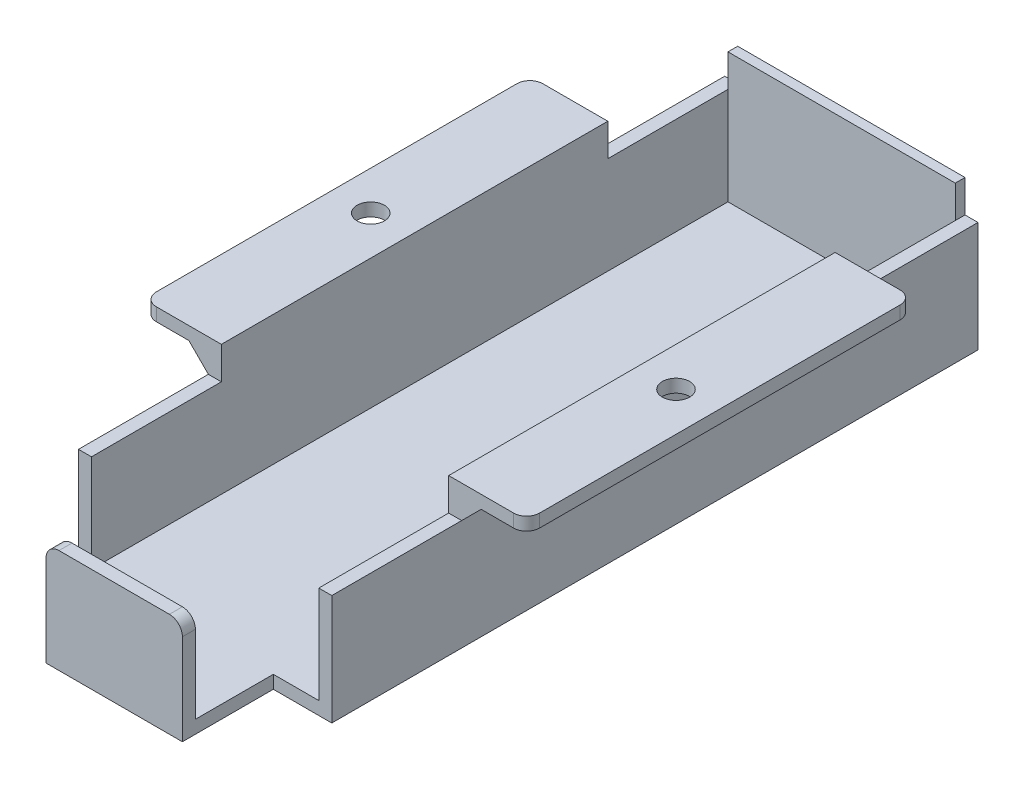
SolidWorks part; units mm, degrees
ref_plane "Front Plane" through (0, 0, 0) normal (0, 0, 1) x (1, 0, 0)
ref_plane "Top Plane" through (0, 0, 0) normal (0, 1, 0) x (1, 0, 0)
ref_plane "Right Plane" through (0, 0, 0) normal (1, 0, 0) x (0, 0, -1)
sketch "Sketch1" plane through (0, 0, 0) normal (0, 0, 1) x (1, 0, 0)
  line L0 (-29.5, 0) -> (-17.5, 0)
  line L1 (-17.5, 0) -> (-17.5, -20)
  line L2 (-17.5, -20) -> (17.5, -20)
  line L3 (0, -618.9467) -> (0, 30328.3864) construction
  line L5 (29.5, -2) -> (29.5, 0)
  line L6 (19.5, -2) -> (29.5, -2)
  line L7 (19.5, -22) -> (19.5, -2)
  line L8 (19.5, -22) -> (-19.5, -22)
  line L9 (-19.5, -22) -> (-19.5, -2)
  line L10 (-19.5, -2) -> (-29.5, -2)
  line L11 (-29.5, -2) -> (-29.5, 0)
  line L12 (17.5, 0) -> (17.5, -20)
  line L13 (29.5, 0) -> (17.5, 0)
  dimension "D1" = 35
  dimension "D2" = 20
  dimension "D3" = 2
  dimension "D4" = 2
  dimension "D5" = 2
  dimension "D6" = 10
extrude "Boss-Extrude1" add sketch "Sketch1" along normal mid plane 98
sketch "Sketch3" plane through (0, 0, 0) normal (1, 0, 0) x (0, 0, -1)
  line L0 (-49, -22) -> (-63, -22)
  line L1 (-63, -22) -> (-63, -6)
  line L2 (-63, -6) -> (-61, -6)
  line L3 (-61, -6) -> (-61, -20)
  line L4 (-61, -20) -> (-49, -20)
  line L5 (-49, -22) -> (-49, -2) construction
  line L6 (-49, -20) -> (-49, -22)
  line L8 (49, -20) -> (49, 0) construction
  dimension "D2" = 2
  dimension "D4" = 16
  dimension "D1" = 110
extrude "Boss-Extrude3" add sketch "Sketch3" along normal mid plane 21
chamfer "Chamfer1" distance 3 angle 45 2 edges at (19.5, -2, 0) (-19.5, -2, 0)
sketch "Sketch4" plane through (0, 0, 0) normal (0, 1, 0) x (1, 0, 0)
  line L0 (-23.5, 0) -> (23.5, 0) construction
  circle A0 centre (-23.5, 0) radius 2.1
  circle A1 centre (23.5, 0) radius 2.1
  point P4 (0, 0)
  dimension "D1" = 4.2
  dimension "D2" = 4.2
  dimension "D3" = 47
extrude "Cut-Extrude1" cut sketch "Sketch4" against normal through all
sketch "Sketch5" plane through (0, -2, 0) normal (0, -1, 0) x (1, 0, 0)
  line L0 (19.5, -49) -> (19.5, 49) construction
  line L1 (27.5, -5) -> (19.5, -5)
  line L2 (27.5, -5) -> (27.5, 5)
  line L3 (27.5, 5) -> (19.5, 5)
  line L4 (19.5, -5) -> (19.5, 5)
  line L5 (27.5, -5) -> (19.5, 5) construction
  line L6 (27.5, 5) -> (19.5, -5) construction
  line L7 (-19.5, 49) -> (-19.5, -49) construction
  line L8 (-27.5, -5) -> (-19.5, -5)
  line L9 (-27.5, -5) -> (-27.5, 5)
  line L10 (-27.5, 5) -> (-19.5, 5)
  line L11 (-19.5, -5) -> (-19.5, 5)
  line L12 (-27.5, -5) -> (-19.5, 5) construction
  line L13 (-27.5, 5) -> (-19.5, -5) construction
  point P0 (23.5, 0)
  point P8 (-23.5, 0)
  dimension "D1" = 10
extrude "Cut-Extrude2" cut sketch "Sketch5" along normal through all
sketch "Sketch2" plane through (0, 0, -49) normal (0, 0, -1) x (-1, 0, 0)
  line L0 (-17.5, 0) -> (17.5, 0)
  line L18 (29.5, -2) -> (29.5, 0)
  line L19 (29.5, 0) -> (17.5, 0)
  line L20 (17.5, 0) -> (17.5, -20)
  line L21 (17.5, -20) -> (-17.5, -20)
  line L22 (-17.5, -20) -> (-17.5, 0)
  line L23 (-17.5, 0) -> (-29.5, 0)
  line L24 (-29.5, 0) -> (-29.5, -2)
  line L25 (-29.5, -2) -> (-22.5, -2)
  line L26 (-22.5, -2) -> (-19.5, -5)
  line L27 (-19.5, -5) -> (-19.5, -22)
  line L28 (-19.5, -22) -> (19.5, -22)
  line L29 (19.5, -22) -> (19.5, -5)
  line L30 (19.5, -5) -> (22.5, -2)
  line L31 (22.5, -2) -> (29.5, -2)
  line L32 (29.5, -2) -> (29.5, 0)
  line L33 (29.5, 0) -> (17.5, 0)
  line L37 (-17.5, 0) -> (-29.5, 0)
  line L38 (-29.5, 0) -> (-29.5, -2)
  line L39 (-29.5, -2) -> (-22.5, -2)
  line L40 (-22.5, -2) -> (-19.5, -5)
  line L41 (-19.5, -5) -> (-19.5, -22)
  line L42 (-19.5, -22) -> (19.5, -22)
  line L43 (19.5, -22) -> (19.5, -5)
  line L44 (19.5, -5) -> (22.5, -2)
  line L45 (22.5, -2) -> (29.5, -2)
  dimension "D1" = 0
extrude "Boss-Extrude5" add sketch "Sketch2" along normal blind 1.5
sketch "Sketch6" plane through (0, 0, 0) normal (0, 1, 0) x (1, 0, 0)
  line L0 (-17.5, -49) -> (-17.5, 49) construction
  line L1 (-29.5, -49) -> (-17.5, -49)
  line L2 (-29.5, -49) -> (-29.5, -29)
  line L3 (-29.5, -29) -> (-17.5, -29)
  line L4 (-17.5, -49) -> (-17.5, -29)
  line L5 (17.5, -49) -> (17.5, 49) construction
  line L6 (29.5, -49) -> (17.5, -49)
  line L7 (29.5, -49) -> (29.5, -29)
  line L8 (29.5, -29) -> (17.5, -29)
  line L9 (17.5, -49) -> (17.5, -29)
  line L11 (29.5, 50.5) -> (17.5, 50.5)
  line L12 (29.5, 50.5) -> (29.5, 30.5)
  line L13 (29.5, 30.5) -> (17.5, 30.5)
  line L14 (17.5, 50.5) -> (17.5, 30.5)
  line L15 (-29.5, 50.5) -> (-17.5, 50.5)
  line L16 (-29.5, 50.5) -> (-29.5, 30.5)
  line L17 (-29.5, 30.5) -> (-17.5, 30.5)
  line L18 (-17.5, 50.5) -> (-17.5, 30.5)
  dimension "D1" = 20
extrude "Cut-Extrude3" cut sketch "Sketch6" against normal up to vertex (5 mm away) up to point (-19.5, -5, 5)
fillet "Fillet1" radius 2 6 edges at (-29.5, -1, 29) (-29.5, -1, -30.5) (29.5, -1, -30.5) (29.5, -1, 29) (-10.5, -6, 62) (10.5, -6, 62)
equation "\"D4@Sketch1\"=\"D3@Sketch1\""
equation "\"D5@Sketch1\"=\"D3@Sketch1\""
equation "\"D2@Sketch3\"=\"D3@Sketch3\""
equation "\"width\"= 24"
equation "\"thk\"= 3"
equation "\"holesize\"= 4.2"
equation "\"holedistance\"= ( 20 + 12 ) / 2"
equation "\"threaded_hole\"= 3.9"
equation "\"fillet_radius\"= 2"
equation "\"ground_clearance\"= 25"
equation "\"tire_thk\"= 3"
equation "\"innerwheel_diam\" = \"wheel_diam\"-2*\"tire_thk\""
equation "\"innerwheel_thk\"= 8"
equation "\"wheel_diam\"= 2*(\"width\"/2+\"ground_clearance\")"
equation "\"coloursensor_holesize\"= 2.65"
equation "\"hole_to_edge\" = 4"
equation "\"D1@Sketch4\"=\"holesize\""
equation "\"D2@Sketch4\"=\"D1@Sketch4\""
